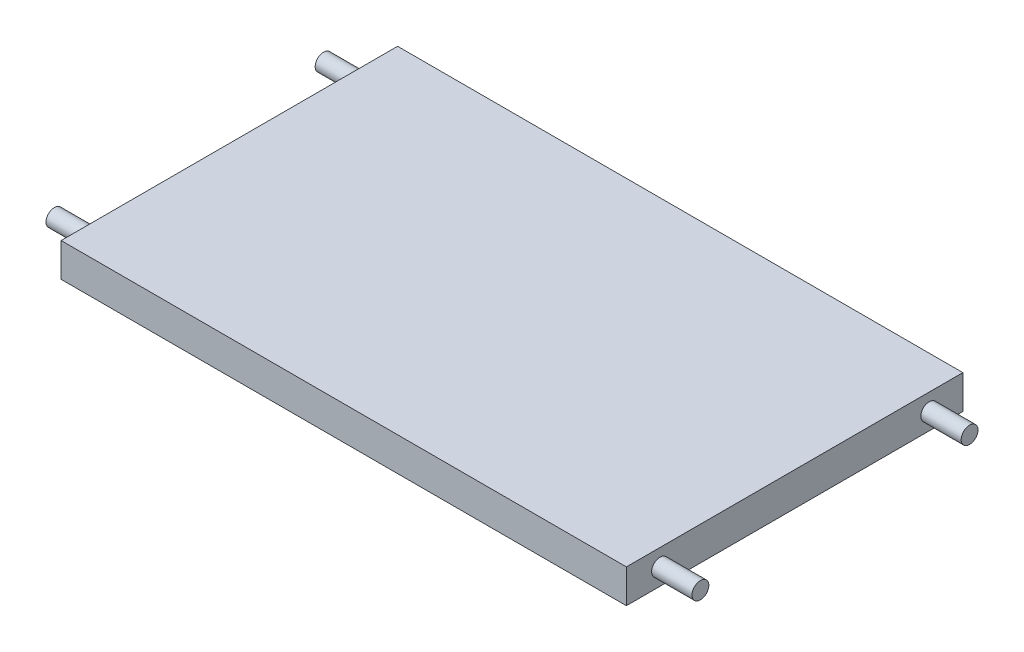
SolidWorks part; units mm, degrees
ref_plane "前视基准面" through (0, 0, 0) normal (0, 0, 1) x (1, 0, 0)
ref_plane "上视基准面" through (0, 0, 0) normal (0, 1, 0) x (1, 0, 0)
ref_plane "右视基准面" through (0, 0, 0) normal (1, 0, 0) x (0, 0, -1)
sketch "草图1" plane through (0, 0, 0) normal (0, 1, 0) x (1, 0, 0)
  line L1 (-84, -50) -> (84, -50)
  line L2 (-84, -50) -> (-84, 50)
  line L3 (-84, 50) -> (84, 50)
  line L4 (84, -50) -> (84, 50)
  line L5 (-84, -50) -> (84, 50) construction
  line L6 (-84, 50) -> (84, -50) construction
  point P0 (0, 0)
  dimension "D1" = 100
  dimension "D2" = 168
extrude "凸台-拉伸1" add sketch "草图1" along normal blind 10
sketch "草图2" plane through (-84, 0, 0) normal (-1, 0, 0) x (0, 0, 1)
  line L0 (-50, 10) -> (50, 0)
  line L1 (50, 10) -> (-50, 0)
  line L2 (0, 5) -> (40, 5)
  line L3 (0, 5) -> (-40, 5)
  line L4 (-50, 0) -> (50, 0)
  line L5 (50, 0) -> (50, 10)
  line L6 (50, 10) -> (-50, 10)
  line L7 (-50, 10) -> (-50, 0)
  line L8 (-50, 0) -> (50, 0)
  line L9 (50, 0) -> (50, 10)
  line L10 (50, 10) -> (-50, 10)
  line L11 (-50, 10) -> (-50, 0)
  circle A0 centre (-40, 5) radius 2.5
  circle A1 centre (40, 5) radius 2.5
  dimension "D4" = 5
  dimension "D5" = 5
  dimension "D2" = 40
  dimension "D3" = 40
  dimension "D1" = 0
extrude "凸台-拉伸2" add sketch "草图2" along normal blind 12 contours A0 | A1
sketch "草图3" plane through (84, 0, 0) normal (1, 0, 0) x (0, 0, -1)
  circle A0 centre (-40, 5) radius 2.5 construction
  circle A1 centre (40, 5) radius 2.5 construction
  circle A2 centre (-40, 5) radius 2.5
  circle A3 centre (40, 5) radius 2.5
extrude "凸台-拉伸3" add sketch "草图3" along normal blind 12
